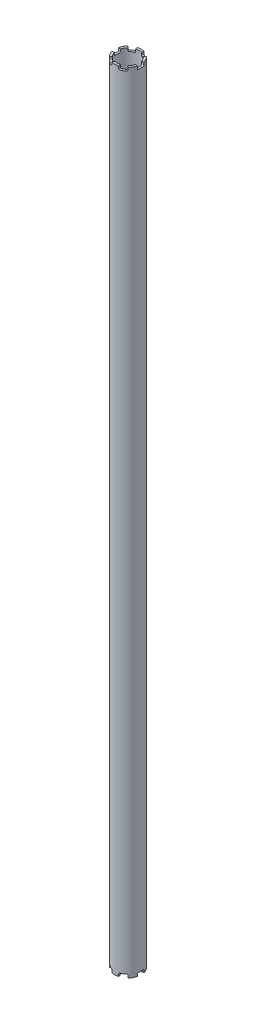
SolidWorks part; units mm, degrees
ref_plane "Front Plane" through (0, 0, 0) normal (0, 0, 1) x (1, 0, 0)
ref_plane "Top Plane" through (0, 0, 0) normal (0, 1, 0) x (1, 0, 0)
ref_plane "Right Plane" through (0, 0, 0) normal (1, 0, 0) x (0, 0, -1)
sketch "Sketch1" plane through (0, 0, 0) normal (0, 1, 0) x (1, 0, 0)
  circle A0 centre (0, 0) radius 30.353
  circle A1 centre (0, 0) radius 25.4
  dimension "D1" = 60.706
  dimension "D2" = 50.8
extrude "Boss-Extrude1" add sketch "Sketch1" along normal blind 1828.8
sketch "Sketch2" plane through (0, 1828.8, 0) normal (0, 1, 0) x (1, 0, 0)
  line L0 (24.5345, 6.574) -> (29.3187, 7.8559)
  line L1 (39.8175, -31.3258) -> (18.82, 47.0377) construction
  line L2 (20.2336, 22.6254) -> (28.8355, -9.4774) construction
  line L3 (0, 0) -> (73.2248, 0) construction
  line L4 (24.5345, -6.574) -> (29.3187, -7.8559)
  line L5 (6.574, -24.5345) -> (7.8559, -29.3187)
  line L6 (17.9605, -17.9605) -> (21.4628, -21.4628)
  line L7 (-17.9605, -17.9605) -> (-21.4628, -21.4628)
  line L8 (-6.574, -24.5345) -> (-7.8559, -29.3187)
  line L9 (-24.5345, 6.574) -> (-29.3187, 7.8559)
  line L10 (-24.5345, -6.574) -> (-29.3187, -7.8559)
  line L11 (-6.574, 24.5345) -> (-7.8559, 29.3187)
  line L12 (-17.9605, 17.9605) -> (-21.4628, 21.4628)
  line L13 (17.9605, 17.9605) -> (21.4628, 21.4628)
  line L14 (6.574, 24.5345) -> (7.8559, 29.3187)
  line L15 (0, 0) -> (24.5345, -6.574) construction
  line L16 (0, 0) -> (6.574, -24.5345) construction
  circle A0 centre (0, 0) radius 25.4 construction
  circle A1 centre (0, 0) radius 30.353 construction
  arc A2 (29.3187, 7.8559) -> (29.3187, -7.8559) centre (0, 0) cw
  arc A3 (24.5345, 6.574) -> (24.5345, -6.574) centre (0, 0) cw
  arc A4 (21.4628, -21.4628) -> (7.8559, -29.3187) centre (0, 0) cw
  arc A5 (17.9605, -17.9605) -> (6.574, -24.5345) centre (0, 0) cw
  arc A6 (-7.8559, -29.3187) -> (-21.4628, -21.4628) centre (0, 0) cw
  arc A7 (-6.574, -24.5345) -> (-17.9605, -17.9605) centre (0, 0) cw
  arc A8 (-29.3187, -7.8559) -> (-29.3187, 7.8559) centre (0, 0) cw
  arc A9 (-24.5345, -6.574) -> (-24.5345, 6.574) centre (0, 0) cw
  arc A10 (-21.4628, 21.4628) -> (-7.8559, 29.3187) centre (0, 0) cw
  arc A11 (-17.9605, 17.9605) -> (-6.574, 24.5345) centre (0, 0) cw
  arc A12 (7.8559, 29.3187) -> (21.4628, 21.4628) centre (0, 0) cw
  arc A13 (6.574, 24.5345) -> (17.9605, 17.9605) centre (0, 0) cw
  point P8 (29.3187, 7.8559)
  point P10 (29.3187, 7.8559)
  point P12 (24.5345, 6.574)
  point P14 (24.5345, 6.574)
  dimension "D2" = 6
  dimension "D1" = 60
  dimension "D3" = 30
extrude "Cut-Extrude2" cut sketch "Sketch2" against normal blind 7.62
fillet "Fillet1" radius 2.54 12 edges at (26.9266, 1821.18, 7.215) (19.7117, 1821.18, 19.7117) (-7.215, 1821.18, 26.9266) (7.215, 1821.18, 26.9266) (26.9266, 1821.18, -7.215) (19.7117, 1821.18, -19.7117) (7.215, 1821.18, -26.9266) (-26.9266, 1821.18, 7.215) (-26.9266, 1821.18, -7.215) (-19.7117, 1821.18, -19.7117) (-7.215, 1821.18, -26.9266) (-19.7117, 1821.18, 19.7117)
ref_plane "Plane4" through (0, 914.4, 0) normal (0, -1, 0) x (-1, 0, 0)
mirror "Mirror1" about plane through (0, 914.4, 0) normal (0, -1, 0) of "Fillet1", "Cut-Extrude2"
